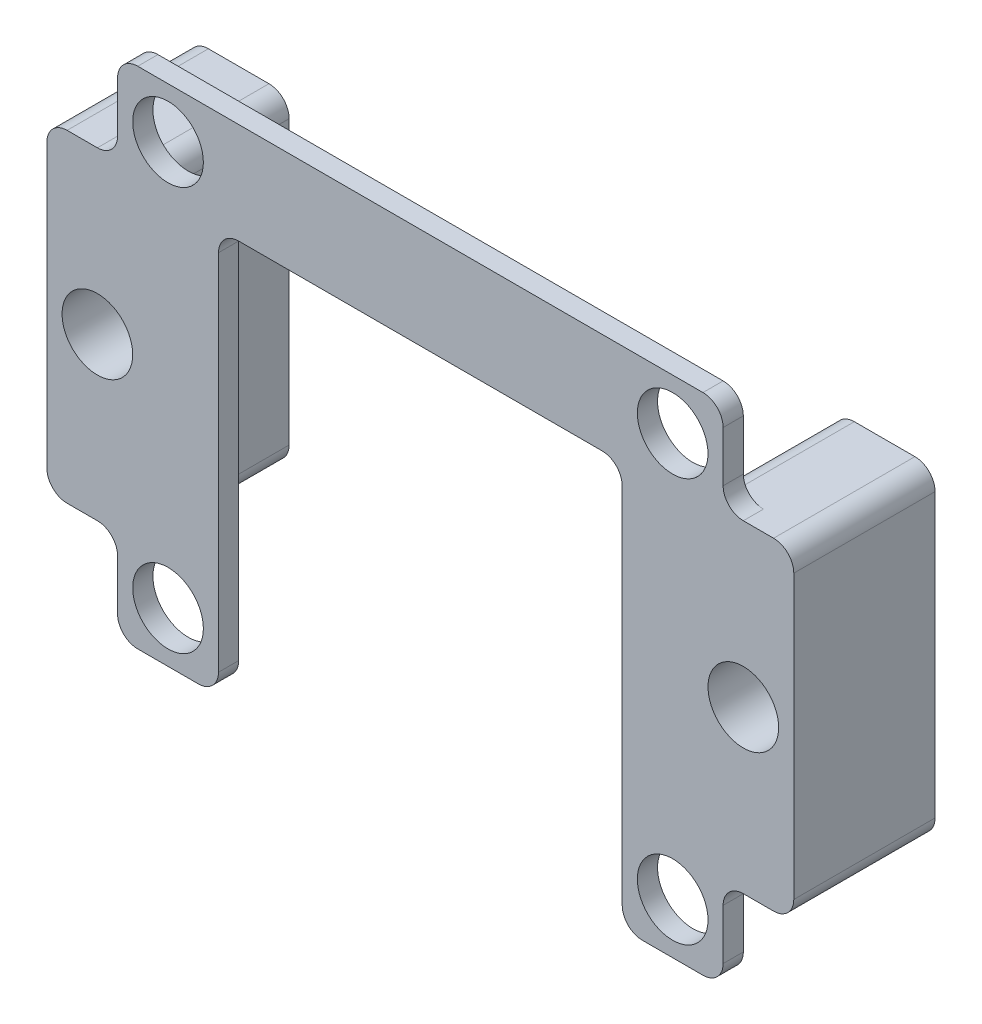
SolidWorks part; units mm, degrees
ref_plane "Front Plane" through (0, 0, 0) normal (0, 0, 1) x (1, 0, 0)
ref_plane "Top Plane" through (0, 0, 0) normal (0, 1, 0) x (1, 0, 0)
ref_plane "Right Plane" through (0, 0, 0) normal (1, 0, 0) x (0, 0, -1)
sketch "Sketch1" plane through (0, 0, 0) normal (0, 0, 1) x (1, 0, 0)
  line L0 (-32, 16) -> (-32, -16) construction
  line L1 (-37, 16) -> (-27, 16)
  line L2 (-37, 16) -> (-37, -16)
  line L3 (-37, -16) -> (-27, -16)
  line L4 (-27, 16) -> (-27, -16)
  line L5 (-32, 0) -> (32, 0) construction
  line L6 (27, 16) -> (37, 16)
  line L7 (27, 16) -> (27, -16)
  line L8 (27, -16) -> (37, -16)
  line L9 (37, 16) -> (37, -16)
  line L10 (32, 16) -> (32, -16) construction
  circle A0 centre (-32, 0) radius 2.4
  circle A1 centre (32, 0) radius 2.4
  dimension "D1" = 4.8
  dimension "D2" = 10
  dimension "D3" = 32
  dimension "D4" = 64
extrude "Boss-Extrude1" add sketch "Sketch1" along normal mid plane 14
sketch "Sketch3" plane through (0, 0, 7) normal (0, 0, 1) x (1, 0, 0)
  line L0 (0, 20) -> (0, -20) construction
  line L1 (-37, 16) -> (-30, 16)
  line L2 (-37, 16) -> (-37, -16)
  line L3 (-37, -16) -> (-30, -16)
  line L4 (37, 16) -> (37, -16)
  line L5 (-25, 20) -> (25, 20) construction
  line L6 (-25, 20) -> (-25, -20) construction
  line L7 (-25, -20) -> (25, -20) construction
  line L8 (25, 20) -> (25, -20) construction
  line L9 (-30, 16) -> (-30, 25)
  line L10 (-30, 25) -> (30, 25)
  line L11 (30, 25) -> (30, 16)
  line L12 (-30, -16) -> (-30, -25)
  line L13 (-30, -25) -> (30, -25)
  line L14 (30, -25) -> (30, -16)
  line L15 (0, 25) -> (0, 20) construction
  line L16 (0, -25) -> (0, -20) construction
  line L17 (30, 16) -> (37, 16)
  line L18 (30, -16) -> (37, -16)
  circle A0 centre (-25, 20) radius 1.6
  circle A1 centre (25, 20) radius 1.6
  circle A2 centre (25, -20) radius 1.6
  circle A3 centre (-25, -20) radius 1.6
  dimension "D1" = 3.2
  dimension "D2" = 50
  dimension "D3" = 40
  dimension "D4" = 60
  dimension "D5" = 50
extrude "Boss-Extrude2" add sketch "Sketch3" against normal blind 2
sketch "Sketch2" plane through (0, 0, 7) normal (0, 0, 1) x (1, 0, 0)
  circle A0 centre (-32, 0) radius 3.5
  circle A1 centre (32, 0) radius 3.5
  circle A2 centre (-25, 20) radius 3.5
  circle A3 centre (25, 20) radius 3.5
  circle A4 centre (25, -20) radius 3.5
  circle A5 centre (-25, -20) radius 3.5
  dimension "D1" = 7
extrude "Cut-Extrude2" cut sketch "Sketch2" against normal blind 6
sketch "Sketch4" plane through (0, 0, 5) normal (0, 0, -1) x (-1, 0, 0)
  line L0 (30, -25) -> (-30, -25) construction
  line L1 (-20, 15) -> (20, 15)
  line L2 (-20, 15) -> (-20, -25)
  line L3 (-20, -25) -> (20, -25)
  line L4 (20, 15) -> (20, -25)
  line L5 (0, 0) -> (0, -25) construction
  dimension "D1" = 40
  dimension "D2" = 40
extrude "Cut-Extrude3" cut sketch "Sketch4" against normal through all
fillet "Fillet1" radius 2 20 edges at (-37, 16, 0) (-37, -16, 0) (-27, -16, -1) (-27, 16, -1) (-30, -25, 6) (30, -25, 6) (30, -16, 6) (27, -16, -1) (37, -16, 0) (30, 16, 6) (37, 16, 0) (27, 16, -1) (-30, 16, 6) (30, 25, 6) (-30, 25, 6) (-30, -16, 6) (-20, 15, 6) (-20, -25, 6) (20, -25, 6) (20, 15, 6)
chamfer "Chamfer1" distance 2 angle 45 2 edges at (-29.6, 0, 1) (34.4, 0, 1)
